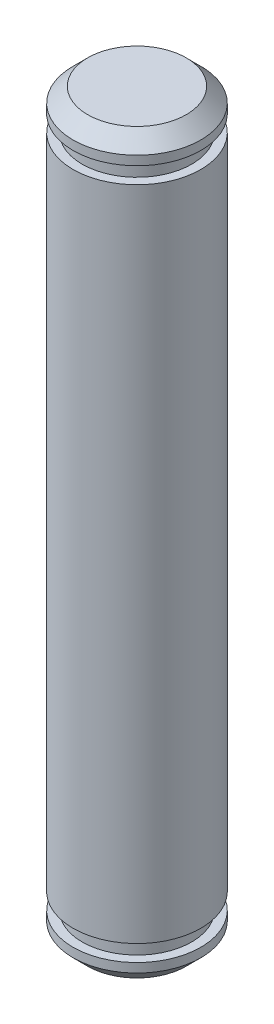
SolidWorks part; units mm, degrees
ref_plane "Face" through (0, 0, 0) normal (0, 0, 1) x (1, 0, 0)
ref_plane "Dessus" through (0, 0, 0) normal (0, 1, 0) x (1, 0, 0)
ref_plane "Droite" through (0, 0, 0) normal (1, 0, 0) x (0, 0, -1)
ref_axis "Axe1" through (0, 35.9935, 0) along (0, -1, 0)
ref_plane "Plan1" through (0, 0, 0) normal (0.9669, 0, -0.2553) x (-0.2553, 0, -0.9669)
sketch "Esquisse1" plane through (0, 0, 0) normal (0.9669, 0, -0.2553) x (-0.2553, 0, -0.9669)
  line L0 (-3.5, 18) -> (-3.5, 11) construction
  line L1 (-3.5, 18) -> (-3.5, -18)
  line L2 (0, 0) -> (-8.4591, 0) construction
  line L3 (-3.5, 18) -> (-3, 18)
  line L4 (-6, 18) -> (6, 18) construction
  line L5 (-3, 18) -> (-3, 18.9)
  line L6 (-3, 18.9) -> (-3.5, 18.9)
  line L7 (-3.5, 18.9) -> (-3.5, 19.4)
  line L8 (-3.5, 19.4) -> (-2.7, 20.2)
  line L9 (-2.7, 20.2) -> (0, 20.2)
  line L10 (0, 35.9935) -> (0, -42.5959) construction
  line L11 (0, 20.2) -> (0, -20.2)
  line L12 (-2.7, -20.2) -> (0, -20.2)
  line L13 (-3.5, -19.4) -> (-2.7, -20.2)
  line L14 (-3.5, -18.9) -> (-3.5, -19.4)
  line L15 (-3, -18.9) -> (-3.5, -18.9)
  line L16 (-3, -18) -> (-3, -18.9)
  line L17 (-3.5, -18) -> (-3, -18)
  line L18 (0, 0) -> (0, -23.5152) construction
  point P24 (-3.5, 0)
  dimension "D1" = 0.9
  dimension "D2" = 0.5
  dimension "D3" = 0.5
  dimension "D4" = 0.8
  dimension "D5" = 45
revolve "Base-Révolution" add sketch "Esquisse1" angle 360 about L18
